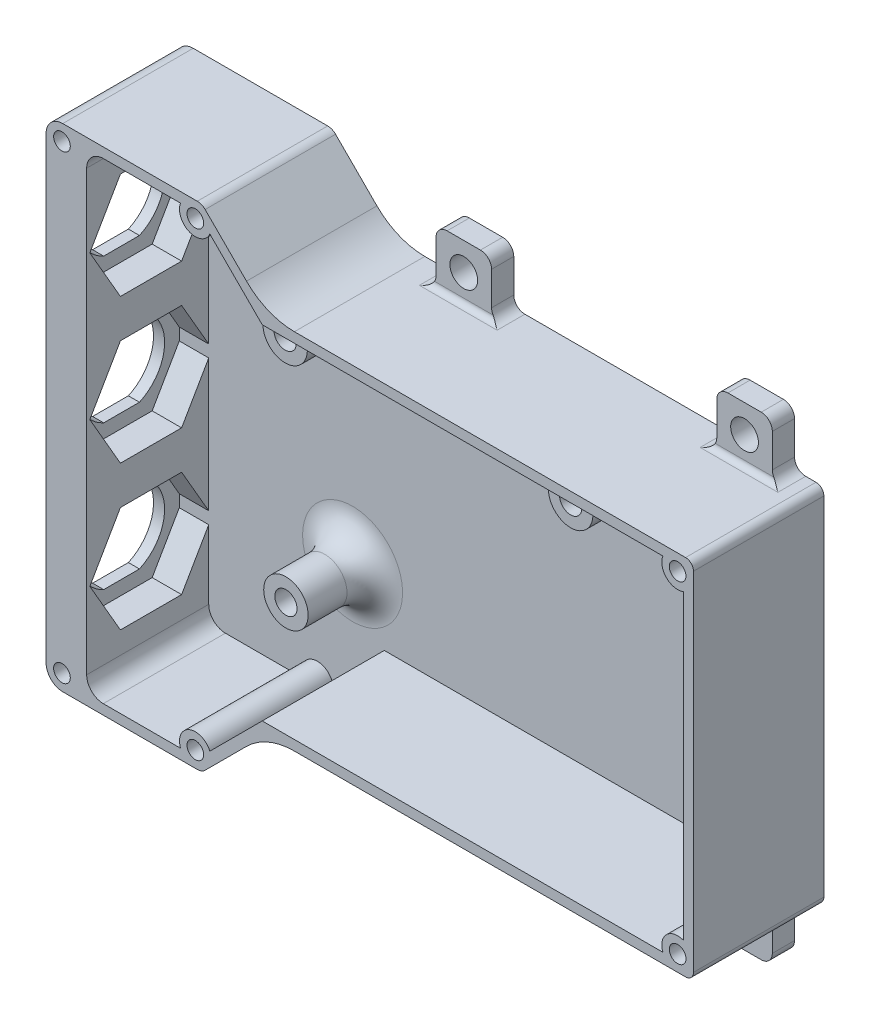
SolidWorks part; units mm, degrees
ref_plane "Front Plane" through (0, 0, 0) normal (0, 0, 1) x (1, 0, 0)
ref_plane "Top Plane" through (0, 0, 0) normal (0, 1, 0) x (1, 0, 0)
ref_plane "Right Plane" through (0, 0, 0) normal (1, 0, 0) x (0, 0, -1)
sketch "Sketch1" plane through (0, 0, 0) normal (0, 0, 1) x (1, 0, 0)
  line L0 (21.6569, -104.2696) -> (33.2669, -92.6596)
  line L1 (21.6569, -11.2696) -> (33.2619, -22.8746)
  line L2 (22.8284, -103.098) -> (34.4384, -91.488) construction
  line L3 (22.8284, -12.4412) -> (34.4334, -24.0462) construction
  line L10 (0, -100.2696) -> (20, -100.2696)
  line L11 (0, -15.2696) -> (20, -15.2696)
  line L12 (20, -100.2696) -> (31.61, -88.6596)
  line L13 (96.455, -88.6596) -> (8, -88.6596) construction
  line L14 (8, -26.8746) -> (96.455, -26.8746) construction
  line L15 (20, -15.2696) -> (31.605, -26.8746)
  line L16 (1.6569, -104.2696) -> (21.6569, -104.2696)
  line L17 (1.6569, -11.2696) -> (21.6569, -11.2696)
  line L24 (96.455, -88.6596) -> (31.61, -88.6596)
  line L26 (31.605, -26.8746) -> (96.455, -26.8746)
  line L27 (96.455, -26.8746) -> (96.455, -88.6596)
  line L28 (100.455, -92.6596) -> (33.2669, -92.6596)
  line L29 (33.2619, -22.8746) -> (100.455, -22.8746)
  line L31 (100.455, -22.8746) -> (100.455, -92.6596)
  line L33 (0, -100.2696) -> (-18.3, -100.2696)
  line L35 (0, -15.2696) -> (-18.3, -15.2696)
  line L36 (-18.3, -15.2696) -> (-18.3, -11.2696)
  line L37 (-18.3, -11.2696) -> (1.6569, -11.2696)
  line L38 (-18.3, -100.2696) -> (-18.3, -104.2696)
  line L39 (-18.3, -104.2696) -> (1.6569, -104.2696)
  line L45 (100.455, -92.6596) -> (4, -92.6596) construction
  line L46 (4, -92.6596) -> (4, -22.8746) construction
  line L47 (4, -22.8746) -> (100.455, -22.8746) construction
  line L52 (8, -88.6596) -> (8, -26.8746) construction
  dimension "D1" = 4
  dimension "D3" = 4
  dimension "D2" = 4
extrude "Boss-Extrude1" add sketch "Sketch1" along normal blind 36.78
sketch "Sketch2" plane through (0, 0, 0) normal (0, 0, -1) x (-1, 0, 0)
  line L0 (18.3, -15.2696) -> (18.3, -100.2696)
  line L16 (-33.2669, -92.6596) -> (-21.6569, -104.2696)
  line L17 (-31.61, -88.6596) -> (-96.455, -88.6596)
  line L18 (-96.455, -88.6596) -> (-96.455, -26.8746)
  line L19 (-96.455, -26.8746) -> (-31.605, -26.8746)
  line L20 (-33.2669, -92.6596) -> (-21.6569, -104.2696)
  line L21 (-20, -15.2696) -> (18.3, -15.2696)
  line L22 (18.3, -15.2696) -> (18.3, -11.2696)
  line L23 (18.3, -11.2696) -> (-21.6569, -11.2696)
  line L24 (-20, -100.2696) -> (-31.61, -88.6596)
  line L25 (-33.2619, -22.8746) -> (-100.455, -22.8746)
  line L26 (-100.455, -22.8746) -> (-100.455, -92.6596)
  line L27 (-100.455, -92.6596) -> (-33.2669, -92.6596)
  line L29 (-21.6569, -104.2696) -> (18.3, -104.2696)
  line L30 (18.3, -104.2696) -> (18.3, -100.2696)
  line L31 (18.3, -100.2696) -> (-20, -100.2696)
  line L33 (-31.605, -26.8746) -> (-20, -15.2696)
  line L35 (-21.6569, -11.2696) -> (-33.2619, -22.8746)
  line L36 (-21.6569, -11.2696) -> (-33.2619, -22.8746)
  line L38 (18.3, -15.2696) -> (18.3, -11.2696)
  line L39 (18.3, -11.2696) -> (-21.6569, -11.2696)
  line L41 (-33.2619, -22.8746) -> (-100.455, -22.8746)
  line L42 (-100.455, -22.8746) -> (-100.455, -92.6596)
  line L43 (-100.455, -92.6596) -> (-33.2669, -92.6596)
  line L45 (-21.6569, -104.2696) -> (18.3, -104.2696)
  line L46 (18.3, -104.2696) -> (18.3, -100.2696)
  dimension "D1" = 0
extrude "Boss-Extrude2" add sketch "Sketch2" against normal blind 3.5
sketch "Sketch4" plane through (-5.3, 0, 0) normal (1, 0, 0) x (0, 0, -1)
  line L0 (-13.8923, -90.5196) -> (-10.7395, -90.5196) construction
  line L1 (-13.8923, -90.5196) -> (-17.0451, -90.5196) construction
  line L2 (-13.8923, -77.0196) -> (-10.7395, -77.0196) construction
  line L3 (-13.8923, -77.0196) -> (-17.0451, -77.0196) construction
  line L4 (-13.8923, -64.5196) -> (-10.7395, -64.5196) construction
  line L5 (-13.8923, -64.5196) -> (-17.0451, -64.5196) construction
  line L6 (-13.8923, -51.0196) -> (-10.7395, -51.0196) construction
  line L7 (-13.8923, -51.0196) -> (-17.0451, -51.0196) construction
  line L8 (-13.8923, -38.5196) -> (-17.0451, -38.5196) construction
  line L9 (-13.8923, -38.5196) -> (-10.7395, -38.5196) construction
  line L10 (-13.8923, -25.0196) -> (-10.7395, -25.0196) construction
  line L11 (-13.8923, -25.0196) -> (-17.0451, -25.0196) construction
  line L12 (-13.8923, -90.5196) -> (-10.7395, -90.5196)
  line L13 (-13.8923, -90.5196) -> (-17.0451, -90.5196)
  line L14 (-13.8923, -77.0196) -> (-10.7395, -77.0196)
  line L15 (-13.8923, -77.0196) -> (-17.0451, -77.0196)
  line L16 (-13.8923, -64.5196) -> (-10.7395, -64.5196)
  line L17 (-13.8923, -64.5196) -> (-17.0451, -64.5196)
  line L18 (-13.8923, -51.0196) -> (-10.7395, -51.0196)
  line L19 (-13.8923, -51.0196) -> (-17.0451, -51.0196)
  line L20 (-13.8923, -38.5196) -> (-17.0451, -38.5196)
  line L21 (-13.8923, -38.5196) -> (-10.7395, -38.5196)
  line L22 (-13.8923, -25.0196) -> (-10.7395, -25.0196)
  line L23 (-13.8923, -25.0196) -> (-17.0451, -25.0196)
  line L24 (-13.8923, -38.8196) -> (-17.111, -38.8196)
  line L25 (-13.8923, -38.8196) -> (-10.6736, -38.8196)
  line L26 (-13.8923, -24.7196) -> (-10.6736, -24.7196)
  line L27 (-13.8923, -24.7196) -> (-17.111, -24.7196)
  line L28 (-13.8923, -64.8196) -> (-17.111, -64.8196)
  line L29 (-13.8923, -64.8196) -> (-10.6736, -64.8196)
  line L30 (-13.8923, -50.7196) -> (-10.6736, -50.7196)
  line L31 (-13.8923, -50.7196) -> (-17.111, -50.7196)
  line L32 (-13.8923, -90.8196) -> (-17.111, -90.8196)
  line L33 (-13.8923, -90.8196) -> (-10.6736, -90.8196)
  line L34 (-13.8923, -76.7196) -> (-10.6736, -76.7196)
  line L35 (-13.8923, -76.7196) -> (-17.111, -76.7196)
  line L36 (-36.78, -100.2696) -> (-3.5, -100.2696)
  line L37 (-36.78, -100.2696) -> (-3.5, -100.2696)
  line L38 (-3.5, -100.2696) -> (-3.5, -15.2696)
  line L39 (-3.5, -100.2696) -> (-3.5, -15.2696)
  line L40 (-3.5, -15.2696) -> (-36.78, -15.2696)
  line L41 (-3.5, -15.2696) -> (-36.78, -15.2696)
  line L42 (-36.78, -15.2696) -> (-36.78, -100.2696)
  arc A0 (-17.0451, -77.0196) -> (-17.0451, -90.5196) centre (-13.8923, -83.7696) ccw construction
  arc A1 (-10.7395, -90.5196) -> (-10.7395, -77.0196) centre (-13.8923, -83.7696) ccw construction
  arc A2 (-10.7395, -64.5196) -> (-10.7395, -51.0196) centre (-13.8923, -57.7696) ccw construction
  arc A3 (-17.0451, -51.0196) -> (-17.0451, -64.5196) centre (-13.8923, -57.7696) ccw construction
  arc A4 (-17.0451, -25.0196) -> (-17.0451, -38.5196) centre (-13.8923, -31.7696) ccw construction
  arc A5 (-10.7395, -38.5196) -> (-10.7395, -25.0196) centre (-13.8923, -31.7696) ccw construction
  arc A6 (-17.0451, -77.0196) -> (-17.0451, -90.5196) centre (-13.8923, -83.7696) ccw
  arc A7 (-10.7395, -90.5196) -> (-10.7395, -77.0196) centre (-13.8923, -83.7696) ccw
  arc A8 (-10.7395, -64.5196) -> (-10.7395, -51.0196) centre (-13.8923, -57.7696) ccw
  arc A9 (-17.0451, -51.0196) -> (-17.0451, -64.5196) centre (-13.8923, -57.7696) ccw
  arc A10 (-17.0451, -25.0196) -> (-17.0451, -38.5196) centre (-13.8923, -31.7696) ccw
  arc A11 (-10.7395, -38.5196) -> (-10.7395, -25.0196) centre (-13.8923, -31.7696) ccw
  arc A12 (-17.111, -24.7196) -> (-17.111, -38.8196) centre (-13.8923, -31.7696) ccw
  arc A13 (-10.6736, -38.8196) -> (-10.6736, -24.7196) centre (-13.8923, -31.7696) ccw
  arc A14 (-17.111, -50.7196) -> (-17.111, -64.8196) centre (-13.8923, -57.7696) ccw
  arc A15 (-10.6736, -64.8196) -> (-10.6736, -50.7196) centre (-13.8923, -57.7696) ccw
  arc A16 (-17.111, -76.7196) -> (-17.111, -90.8196) centre (-13.8923, -83.7696) ccw
  arc A17 (-10.6736, -90.8196) -> (-10.6736, -76.7196) centre (-13.8923, -83.7696) ccw
  line M1 (-21.5451, -64.5196) -> (-18.3923, -64.5196)
  arc M2 (-18.3923, -64.5196) -> (-18.3923, -51.0196) centre (-18.3923, -57.7696) cw
  line M3 (-18.3923, -51.0196) -> (-21.5451, -51.0196)
  arc M4 (-21.5451, -51.0196) -> (-21.5451, -64.5196) centre (-18.3923, -57.7696) ccw
  dimension "D1" = 0.3
extrude "Boss-Extrude3" add sketch "Sketch4" against normal blind 2 contours L41 L42 L37 L39 A17 L33 L32 A16 L35 L34 A15 L29 L28 A14 L31 L30 A13 L25 L24 A12 L27 L26 M1 M4 M3 M2 | M4 M1 M2 M3 region at (-5.3, -57.7696, 35.8672) region at (-5.3, -57.7696, 25.6881)
sketch "Sketch5" plane through (-5.3, 0, 0) normal (1, 0, 0) x (0, 0, -1)
  line L18 (-13.8923, -24.7196) -> (-13.8923, -38.8196)
  line L19 (-10.6736, -24.7196) -> (-17.111, -24.7196) construction
  line L20 (-17.111, -38.8196) -> (-10.6736, -38.8196) construction
  line L21 (-13.8923, -50.7196) -> (-13.8923, -64.8196)
  line L22 (-10.6736, -50.7196) -> (-17.111, -50.7196) construction
  line L23 (-17.111, -64.8196) -> (-10.6736, -64.8196) construction
  line L24 (-13.8923, -76.7196) -> (-13.8923, -90.8196)
  line L25 (-10.6736, -76.7196) -> (-17.111, -76.7196) construction
  line L26 (-17.111, -90.8196) -> (-10.6736, -90.8196) construction
  line L27 (-24.9116, -83.7696) -> (-19.402, -93.3126)
  line L28 (-24.7384, -31.7696) -> (-19.3154, -41.1626)
  line L29 (-19.3154, -41.1626) -> (-8.4692, -41.1626)
  line L30 (-8.4692, -41.1626) -> (-3.0462, -31.7696)
  line L31 (-3.0462, -31.7696) -> (-8.4692, -22.3766)
  line L32 (-8.4692, -22.3766) -> (-19.3154, -22.3766)
  line L33 (-19.3154, -22.3766) -> (-24.7384, -31.7696)
  line L34 (-24.7384, -57.7696) -> (-19.3154, -67.1626)
  line L35 (-19.3154, -67.1626) -> (-8.4692, -67.1626)
  line L36 (-36.78, -100.2696) -> (-3.5, -100.2696) construction
  line L37 (-36.78, -15.2696) -> (-36.78, -100.2696) construction
  line L38 (-3.5, -15.2696) -> (-36.78, -15.2696) construction
  line L39 (-3.5, -100.2696) -> (-3.5, -15.2696) construction
  line L40 (-36.78, -100.2696) -> (-3.5, -100.2696)
  line L41 (-36.78, -15.2696) -> (-36.78, -100.2696)
  line L42 (-3.5, -15.2696) -> (-36.78, -15.2696)
  line L43 (-3.5, -100.2696) -> (-3.5, -15.2696)
  line L44 (-8.4692, -67.1626) -> (-3.0462, -57.7696)
  line L45 (-3.0462, -57.7696) -> (-8.4692, -48.3766)
  line L46 (-8.4692, -48.3766) -> (-19.3154, -48.3766)
  line L47 (-19.3154, -48.3766) -> (-24.7384, -57.7696)
  line L48 (-24.7384, -83.7696) -> (-19.3154, -93.1626)
  line L49 (-19.3154, -93.1626) -> (-8.4692, -93.1626)
  line L50 (-8.4692, -93.1626) -> (-3.0462, -83.7696)
  line L51 (-3.0462, -83.7696) -> (-8.4692, -74.3766)
  line L52 (-8.4692, -74.3766) -> (-19.3154, -74.3766)
  line L53 (-19.3154, -74.3766) -> (-24.7384, -83.7696)
  line L54 (-19.402, -93.3126) -> (-8.3826, -93.3126)
  line L55 (-8.3826, -93.3126) -> (-2.873, -83.7696)
  line L56 (-2.873, -83.7696) -> (-8.3826, -74.2266)
  line L57 (-8.3826, -74.2266) -> (-19.402, -74.2266)
  line L58 (-19.402, -74.2266) -> (-24.9116, -83.7696)
  line L59 (-19.402, -22.2266) -> (-24.9116, -31.7696)
  line L60 (-24.9116, -31.7696) -> (-19.402, -41.3126)
  line L61 (-19.402, -41.3126) -> (-8.3826, -41.3126)
  line L62 (-8.3826, -41.3126) -> (-2.873, -31.7696)
  line L63 (-2.873, -31.7696) -> (-8.3826, -22.2266)
  line L64 (-8.3826, -22.2266) -> (-19.402, -22.2266)
  line L65 (-19.402, -48.2266) -> (-24.9116, -57.7696)
  line L66 (-24.9116, -57.7696) -> (-19.402, -67.3126)
  line L67 (-19.402, -67.3126) -> (-8.3826, -67.3126)
  line L68 (-8.3826, -67.3126) -> (-2.873, -57.7696)
  line L69 (-2.873, -57.7696) -> (-8.3826, -48.2266)
  line L70 (-8.3826, -48.2266) -> (-19.402, -48.2266)
  circle A0 centre (-13.8923, -31.7696) radius 9.393 construction
  circle A1 centre (-13.8923, -57.7696) radius 9.393 construction
  circle A2 centre (-13.8923, -83.7696) radius 9.393 construction
  line M16 (-3.5, -15.2696) -> (-36.78, -15.2696)
  line M17 (-36.78, -15.2696) -> (-36.78, -100.2696)
  line M18 (-36.78, -100.2696) -> (-3.5, -100.2696)
  line M19 (-3.5, -100.2696) -> (-3.5, -15.2696)
  dimension "D1" = 0.15
extrude "Boss-Extrude4" add sketch "Sketch5" along normal up to surface (5.3 mm away) contours L46 L45 L44 L34 L32 L30 L29 L28 M19 M16 M17 M18 region at (-5.3, -88.9975, 22.9473)
sketch "Sketch6" plane through (0, 0, 36.78) normal (0, 0, 1) x (1, 0, 0)
  line L1 (-48.9743, 0) -> (133.8378, 0)
  line L2 (-48.9743, 0) -> (-48.9743, -122.4446)
  line L3 (-48.9743, -122.4446) -> (133.8378, -122.4446)
  line L4 (133.8378, 0) -> (133.8378, -122.4446)
extrude "Cut-Extrude1" cut sketch "Sketch6" against normal blind 4
ref_plane "Plane1" through (5, 0, 0) normal (1, 0, 0) x (0, 0, -1)
fillet "Fillet4" radius 10 2 edges at (33.2669, -92.6596, 16.39) (33.2619, -22.8746, 16.39)
sketch "Sketch8" plane through (0, 0, 32.78) normal (0, 0, 1) x (1, 0, 0)
  line L0 (100.455, -92.6596) -> (100.455, -22.8746) construction
  line L3 (100.455, -88.6596) -> (100.455, -26.8746)
  line L6 (96.455, -26.8746) -> (96.455, -88.6596)
  line L7 (96.455, -26.8746) -> (100.455, -26.8746)
  line L8 (96.455, -88.6596) -> (100.455, -88.6596)
extrude "Cut-Extrude2" cut sketch "Sketch8" against normal up to surface (29.28 mm away) up to face at (13.2163, -57.7691, 3.5)
sketch "Sketch9" plane through (100.455, 0, 0) normal (1, 0, 0) x (0, 0, -1)
  line L0 (-32.78, -92.6596) -> (-32.78, -88.6596) construction
  line L1 (-3.5, -88.6596) -> (-32.78, -88.6596) construction
  line L2 (-32.78, -92.6596) -> (0, -92.6596) construction
  line L3 (0, -92.6596) -> (0, -22.8746) construction
  line L4 (-3.5, -88.6596) -> (-3.5, -26.8746) construction
  line L5 (-3.5, -26.8746) -> (-32.78, -26.8746) construction
  line L6 (-32.78, -26.8746) -> (-32.78, -22.8746) construction
  line L7 (-32.78, -22.8746) -> (0, -22.8746) construction
  line L8 (-32.78, -92.6596) -> (-32.78, -88.6596)
  line L9 (-3.5, -88.6596) -> (-32.78, -88.6596)
  line L10 (-32.78, -92.6596) -> (0, -92.6596)
  line L11 (0, -92.6596) -> (0, -22.8746)
  line L12 (-3.5, -88.6596) -> (-3.5, -26.8746)
  line L13 (-3.5, -26.8746) -> (-32.78, -26.8746)
  line L14 (-32.78, -26.8746) -> (-32.78, -22.8746)
  line L15 (-32.78, -22.8746) -> (0, -22.8746)
extrude "Boss-Extrude6" add sketch "Sketch9" along normal blind 11
sketch "Sketch10" plane through (0, 0, 32.78) normal (0, 0, 1) x (1, 0, 0)
  line L0 (111.455, -88.6596) -> (31.61, -88.6596) construction
  line L2 (31.605, -26.8746) -> (111.455, -26.8746) construction
  line L4 (111.455, -88.6596) -> (107.455, -88.6596)
  line L6 (107.455, -26.8746) -> (111.455, -26.8746)
  line L8 (111.455, -26.8746) -> (107.455, -26.8746)
  line L9 (107.455, -26.8746) -> (107.455, -88.6596)
  line L10 (111.455, -26.8746) -> (111.455, -88.6596)
  line M1 (31.605, -26.8746) -> (111.455, -26.8746)
  line M19 (111.455, -88.6596) -> (31.61, -88.6596)
extrude "Boss-Extrude7" add sketch "Sketch10" against normal up to surface (29.28 mm away) contours L10 L9 M1 M19 region at (109.455, -57.7671, 32.78) up to face at (-12.8, -57.7696, 3.5)
sketch "Sketch24" plane through (0, 0, 32.78) normal (0, 0, 1) x (1, 0, 0)
  line L2 (111.455, -22.8746) -> (37.404, -22.8746) construction
  line L3 (111.455, -22.8746) -> (111.455, -92.6596) construction
  line L4 (31.605, -26.8746) -> (107.455, -26.8746) construction
  line L5 (107.455, -26.8746) -> (107.455, -88.6596) construction
  line L6 (111.455, -22.8746) -> (37.404, -22.8746)
  line L7 (111.455, -22.8746) -> (111.455, -92.6596)
  line L8 (31.605, -26.8746) -> (107.455, -26.8746)
  line L9 (107.455, -26.8746) -> (107.455, -88.6596)
  line L10 (107.455, -26.8746) -> (107.455, -29.8746)
  line L11 (107.455, -26.8746) -> (104.455, -26.8746)
  line L12 (104.455, -26.8746) -> (107.455, -29.8746)
  line L13 (107.455, -88.6596) -> (104.455, -88.6596)
  line L14 (107.455, -88.6596) -> (31.61, -88.6596) construction
  line L15 (104.455, -88.6596) -> (107.455, -85.6596)
  line M1 (107.455, -26.8746) -> (107.455, -88.6596)
  line M2 (107.455, -88.6596) -> (31.61, -88.6596)
extrude "Boss-Extrude10" add sketch "Sketch24" against normal up to surface (29.28 mm away) contours L15 M2 M1 | L8 L12 M1 region at (106.455, -87.6596, 32.78) region at (106.455, -27.8746, 32.78) up to face at (-12.8, -57.7696, 3.5)
sketch "Sketch28" plane through (0, 0, 32.78) normal (0, 0, 1) x (1, 0, 0)
  line L1 (-7.3, -83.7696) -> (-7.3, -31.7696)
  line L2 (-7.3, -31.7696) -> (-7.3, -6.2489)
  line L3 (-7.3, -6.2489) -> (-26.3455, -6.2489)
  line L4 (-26.3455, -6.2489) -> (-26.3455, -107.7031)
  line L5 (-26.3455, -107.7031) -> (-7.3, -107.7031)
  line L6 (-7.3, -107.7031) -> (-7.3, -83.7696)
extrude "Cut-Extrude12" cut sketch "Sketch28" against normal through all
sketch "Sketch29" plane through (0, 0, 32.78) normal (0, 0, 1) x (1, 0, 0)
  line L0 (-7.3, -104.2696) -> (21.6569, -104.2696) construction
  line L1 (21.6569, -104.2696) -> (30.3379, -95.5885) construction
  line L2 (37.409, -92.6596) -> (111.455, -92.6596) construction
  line L3 (111.455, -22.8746) -> (111.455, -92.6596) construction
  line L4 (111.455, -22.8746) -> (37.404, -22.8746) construction
  line L5 (30.3329, -19.9457) -> (21.6569, -11.2696) construction
  line L6 (21.6569, -11.2696) -> (-7.3, -11.2696) construction
  line L7 (-7.3, -104.2696) -> (21.6569, -104.2696)
  line L8 (21.6569, -104.2696) -> (30.3379, -95.5885)
  line L9 (37.409, -92.6596) -> (111.455, -92.6596)
  line L10 (111.455, -22.8746) -> (111.455, -92.6596)
  line L11 (111.455, -22.8746) -> (37.404, -22.8746)
  line L12 (30.3329, -19.9457) -> (21.6569, -11.2696)
  line L13 (21.6569, -11.2696) -> (-7.3, -11.2696)
  line L14 (-7.3, -102.0736) -> (20.7472, -102.0736)
  line L15 (20.7472, -102.0736) -> (28.7851, -94.0357)
  line L16 (37.409, -90.4636) -> (109.259, -90.4636)
  line L17 (109.259, -25.0706) -> (109.259, -90.4636)
  line L18 (109.259, -25.0706) -> (37.404, -25.0706)
  line L19 (28.7801, -21.4985) -> (20.7472, -13.4656)
  line L20 (20.7472, -13.4656) -> (-7.3, -13.4656)
  line L21 (-7.3, -13.4656) -> (-7.3, -11.2696)
  line L22 (-7.3, -102.0736) -> (-7.3, -104.2696)
  arc A0 (37.409, -92.6596) -> (30.3379, -95.5885) centre (37.409, -102.6596) ccw construction
  arc A1 (30.3329, -19.9457) -> (37.404, -22.8746) centre (37.404, -12.8746) ccw construction
  arc A2 (37.409, -92.6596) -> (30.3379, -95.5885) centre (37.409, -102.6596) ccw
  arc A3 (30.3329, -19.9457) -> (37.404, -22.8746) centre (37.404, -12.8746) ccw
  arc A4 (37.409, -90.4636) -> (28.7851, -94.0357) centre (37.409, -102.6596) ccw
  arc A5 (28.7801, -21.4985) -> (37.404, -25.0706) centre (37.404, -12.8746) ccw
  dimension "D1" = 2.196
extrude "Cut-Extrude13" cut sketch "Sketch29" against normal through all
sketch "Sketch30" plane through (0, 0, 0) normal (0, 0, -1) x (-1, 0, 0)
  line L0 (-37.404, -25.0706) -> (-109.259, -25.0706) construction
  line L1 (-109.259, -25.0706) -> (-109.259, -90.4636) construction
  line L2 (-109.259, -90.4636) -> (-37.409, -90.4636) construction
  line L3 (-28.7851, -94.0357) -> (-20.7472, -102.0736) construction
  line L4 (-20.7472, -102.0736) -> (7.3, -102.0736) construction
  line L5 (7.3, -102.0736) -> (7.3, -13.4656) construction
  line L6 (7.3, -13.4656) -> (-20.7472, -13.4656) construction
  line L7 (-20.7472, -13.4656) -> (-28.7801, -21.4985) construction
  line L8 (-109.259, -25.0706) -> (-109.259, -90.4636)
  line L9 (-109.259, -90.4636) -> (-37.409, -90.4636)
  line L10 (-28.7851, -94.0357) -> (-20.7472, -102.0736)
  line L11 (-20.7472, -102.0736) -> (7.3, -102.0736)
  line L12 (7.3, -102.0736) -> (7.3, -13.4656)
  line L13 (7.3, -13.4656) -> (-20.7472, -13.4656)
  line L14 (-20.7472, -13.4656) -> (-28.7801, -21.4985)
  line L15 (-37.404, -25.0706) -> (-109.259, -25.0706)
  arc A0 (-28.7851, -94.0357) -> (-37.409, -90.4636) centre (-37.409, -102.6596) ccw construction
  arc A1 (-37.404, -25.0706) -> (-28.7801, -21.4985) centre (-37.404, -12.8746) ccw construction
  arc A2 (-28.7851, -94.0357) -> (-37.409, -90.4636) centre (-37.409, -102.6596) ccw
  arc A3 (-37.404, -25.0706) -> (-28.7801, -21.4985) centre (-37.404, -12.8746) ccw
extrude "Cut-Extrude14" cut sketch "Sketch30" against normal blind 2
fillet "Fillet26" radius 3 2 edges at (-7.3, -13.4656, 17.39) (-7.3, -102.0736, 17.39)
fillet "Fillet27" radius 3 2 edges at (0, -100.2696, 18.14) (0, -15.2696, 18.14)
fillet "Fillet28" radius 2 4 edges at (20, -15.2696, 18.14) (20.7472, -13.4656, 17.39) (20, -100.2696, 18.14) (20.7472, -102.0736, 17.39) tangent propagation no
sketch "Sketch33" plane through (0, 0, 32.78) normal (0, 0, 1) x (1, 0, 0)
  line L2 (109.259, -25.0706) -> (109.259, -90.4636) construction
  line L3 (109.259, -90.4636) -> (37.409, -90.4636) construction
  line L4 (19.9188, -102.0736) -> (-4.3, -102.0736) construction
  line L5 (28.7851, -94.0357) -> (21.333, -101.4878) construction
  line L6 (-4.3, -13.4656) -> (19.9188, -13.4656) construction
  line L7 (21.333, -14.0514) -> (28.7801, -21.4985) construction
  line L8 (-7.3, -99.0736) -> (-7.3, -16.4656) construction
  line L9 (37.404, -25.0706) -> (109.259, -25.0706) construction
  circle A0 centre (106.406, -27.9236) radius 1.5
  circle A1 centre (106.406, -27.9236) radius 2.853
  circle A2 centre (106.406, -87.6106) radius 2.853
  circle A3 centre (19.5655, -99.2206) radius 2.853
  circle A4 centre (19.5655, -16.3186) radius 2.853
  circle A5 centre (-4.447, -16.3186) radius 2.853
  circle A6 centre (-4.447, -99.2206) radius 2.853
  dimension "D3" = 3
  dimension "D4" = 5.706
  dimension "D2" = 2.853
extrude "Boss-Extrude13" add sketch "Sketch33" against normal up to surface (29.28 mm away) contours A4 | A3 | A2 | A1 up to face at (20.7548, -57.769, 3.5)
sketch "Sketch34" plane through (0, 0, 32.78) normal (0, 0, 1) x (1, 0, 0)
  circle A0 centre (106.406, -27.9236) radius 2.853 construction
  circle A1 centre (106.406, -87.6106) radius 2.853 construction
  circle A2 centre (19.5655, -99.2206) radius 2.853 construction
  circle A3 centre (-4.447, -99.2206) radius 2.853 construction
  circle A4 centre (19.5655, -16.3186) radius 2.853 construction
  circle A5 centre (-4.447, -16.3186) radius 2.853 construction
  circle A6 centre (106.406, -27.9236) radius 2.853
  circle A7 centre (106.406, -87.6106) radius 2.853
  circle A8 centre (19.5655, -99.2206) radius 2.853
  circle A9 centre (-4.447, -99.2206) radius 2.853
  circle A10 centre (19.5655, -16.3186) radius 2.853
  circle A11 centre (-4.447, -16.3186) radius 2.853
  circle A12 centre (-4.447, -16.3186) radius 1.5
  circle A13 centre (19.5655, -16.3186) radius 1.5
  circle A14 centre (106.406, -27.9236) radius 1.5
  circle A15 centre (106.406, -87.6106) radius 1.5
  circle A16 centre (19.5655, -99.2206) radius 1.5
  circle A17 centre (-4.447, -99.2206) radius 1.5
extrude "Cut-Extrude15" cut sketch "Sketch34" against normal blind 20 contours A12 | A13 | A14 | A15 | A16 | A17
fillet "Fillet29" radius 1.425 2 edges at (109.259, -25.0706, 17.39) (109.259, -90.4636, 17.39)
ref_plane "Plane2" through (0, 0, 20.78) normal (0, 0, 1) x (1, 0, 0)
sketch "Sketch35" plane through (0, 0, 20.78) normal (0, 0, 1) x (1, 0, 0)
  line L0 (31.61, -88.6596) -> (103.7528, -88.6596) construction
  line L1 (107.455, -30.5767) -> (107.455, -84.9574) construction
  line L2 (103.7528, -26.8746) -> (31.605, -26.8746) construction
  line L3 (31.61, -88.6596) -> (103.7528, -88.6596)
  line L4 (107.455, -30.5767) -> (107.455, -84.9574)
  line L5 (103.7528, -26.8746) -> (31.605, -26.8746)
  line L6 (107.455, -84.9574) -> (107.455, -88.6596)
  line L7 (107.455, -88.6596) -> (103.7528, -88.6596)
  line L8 (103.7528, -26.8746) -> (107.455, -26.8746)
  line L9 (107.455, -26.8746) -> (107.455, -30.5767)
  line L10 (31.605, -26.8746) -> (31.61, -88.6596)
extrude "Cut-Extrude16" cut sketch "Sketch35" against normal up to surface (17.28 mm away) up to face at (20.4692, -57.769, 3.5)
sketch "Sketch36" plane through (0, 0, 32.78) normal (0, 0, 1) x (1, 0, 0)
  line L1 (-22.7026, -2.6518) -> (121.9699, -2.6518)
  line L2 (-22.7026, -2.6518) -> (-22.7026, -112.3259)
  line L3 (-22.7026, -112.3259) -> (121.9699, -112.3259)
  line L4 (121.9699, -2.6518) -> (121.9699, -112.3259)
extrude "Cut-Extrude17" cut sketch "Sketch36" against normal blind 7.3
sketch "Sketch38" plane through (0, 0, 3.5) normal (0, 0, 1) x (1, 0, 0)
  circle A2 centre (25.7592, -36.7486) radius 2
  circle A4 centre (77.1688, -36.7486) radius 2
  circle A6 centre (25.8989, -78.0236) radius 2
  circle A7 centre (102.7085, -78.0236) radius 4
  circle A8 centre (102.7085, -78.0236) radius 2
  circle A9 centre (77.1688, -36.7486) radius 4
  circle A10 centre (25.7592, -36.7486) radius 4
  circle A11 centre (25.8989, -78.0236) radius 4
  dimension "D1" = 2
extrude "Boss-Extrude14" add sketch "Sketch38" along normal up to surface (12 mm away) contours A7 A8 | A11 A6 | A10 A2 | A9 A4 region at (98.8216, -78.0236, 3.5) region at (73.2819, -36.7486, 3.5) region at (21.8723, -36.7486, 3.5) region at (22.012, -78.0236, 3.5)
fillet "Fillet30" radius 5 4 edges at (98.7085, -78.0236, 3.5) (73.1688, -36.7486, 3.5) (21.7592, -36.7486, 3.5) (21.8989, -78.0236, 3.5)
sketch "Sketch39" plane through (0, 0, 2) normal (0, 0, -1) x (-1, 0, 0)
  line L0 (-107.834, -90.4636) -> (-37.409, -90.4636) construction
  line L1 (-37.404, -25.0706) -> (-107.834, -25.0706) construction
  line L2 (-107.834, -90.4636) -> (-37.409, -90.4636)
  line L3 (-37.404, -25.0706) -> (-107.834, -25.0706)
  line L4 (-103.9747, -25.0706) -> (-103.9747, -15.0706)
  line L5 (-103.9747, -15.0706) -> (-93.9747, -15.0706)
  line L6 (-93.9747, -15.0706) -> (-93.9747, -25.0706)
  line L7 (-53.4219, -25.0706) -> (-53.4219, -15.0706)
  line L8 (-53.4219, -15.0706) -> (-43.4219, -15.0706)
  line L9 (-43.4219, -15.0706) -> (-43.4219, -25.0706)
  line L10 (-109.259, -57.7671) -> (-21.9967, -57.7671)
  line L11 (-109.259, -26.4956) -> (-109.259, -89.0386) construction
  line L12 (-37.404, -90.4636) -> (-107.834, -90.4636)
  line L13 (-43.4219, -100.4636) -> (-43.4219, -90.4636)
  line L14 (-53.4219, -100.4636) -> (-43.4219, -100.4636)
  line L15 (-53.4219, -90.4636) -> (-53.4219, -100.4636)
  line L16 (-103.9747, -90.4636) -> (-103.9747, -100.4636)
  line L17 (-103.9747, -100.4636) -> (-93.9747, -100.4636)
  line L18 (-93.9747, -100.4636) -> (-93.9747, -90.4636)
  circle A0 centre (-98.9747, -20.0706) radius 2.5
  circle A1 centre (-48.4219, -20.0706) radius 2.5
  circle A2 centre (-48.4219, -95.4636) radius 2.5
  circle A3 centre (-98.9747, -95.4636) radius 2.5
extrude "Boss-Extrude15" add sketch "Sketch39" against normal blind 4 contours L9 L8 L7 L3 A1 | L6 L5 L4 L3 A0 | L17 L18 L12 L16 A3 | L12 L15 L14 L13 A2 region at (48.4219, -90.605, 2) region at (98.9747, -90.605, 2) region at (98.9747, -24.9292, 2) region at (48.4219, -24.9292, 2)
fillet "Fillet31" radius 2 16 edges at (53.4219, -100.4636, 4) (53.4219, -90.4636, 4) (43.4219, -90.4636, 4) (43.4219, -100.4636, 4) (93.9747, -90.4636, 4) (93.9747, -100.4636, 4) (103.9747, -100.4636, 4) (103.9747, -90.4636, 4) (103.9747, -25.0706, 4) (103.9747, -15.0706, 4) (93.9747, -15.0706, 4) (93.9747, -25.0706, 4) (43.4219, -25.0706, 4) (53.4219, -25.0706, 4) (43.4219, -15.0706, 4) (53.4219, -15.0706, 4)
fillet "Fillet32" radius 1 4 edges at (48.4219, -25.0706, 6) (98.9747, -25.0706, 6) (98.9747, -90.4636, 6) (48.4219, -90.4636, 6)
